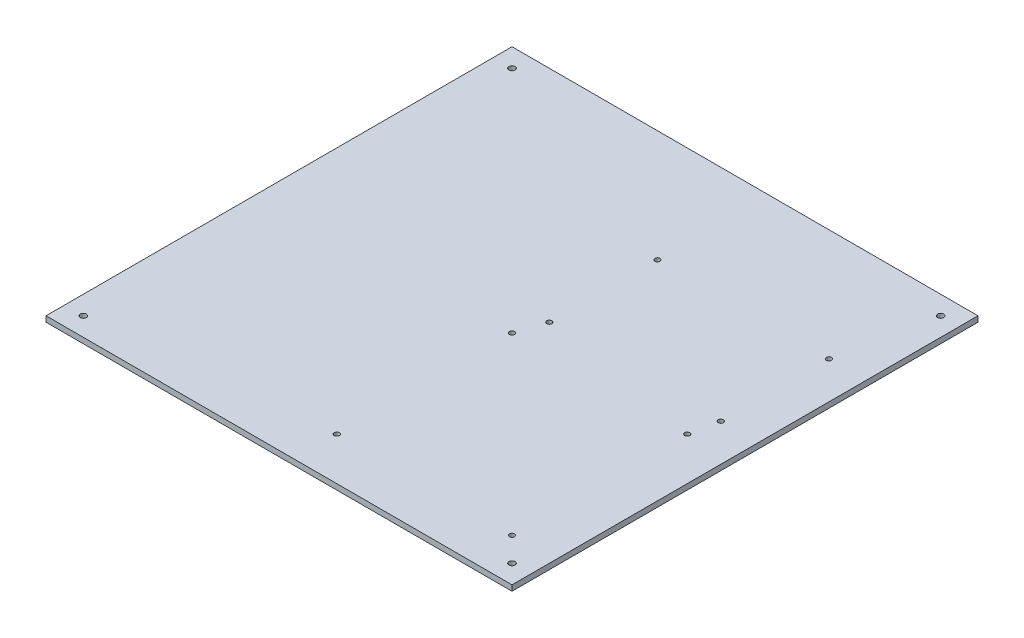
SolidWorks part; units mm, degrees
ref_plane "Front Plane" through (0, 0, 0) normal (0, 0, 1) x (1, 0, 0)
ref_plane "Top Plane" through (0, 0, 0) normal (0, 1, 0) x (1, 0, 0)
ref_plane "Right Plane" through (0, 0, 0) normal (1, 0, 0) x (0, 0, -1)
sketch "Sketch1" plane through (0, 0, 0) normal (0, 1, 0) x (1, 0, 0)
  line L0 (0, 0) -> (0, -250) construction
  line L1 (-125, 0) -> (125, 0)
  line L2 (-125, 0) -> (-125, -250)
  line L3 (-125, -250) -> (125, -250)
  line L4 (125, 0) -> (125, -250)
  line L5 (0, -1.65) -> (0, 1.65) construction
  line L6 (-125, -125) -> (125, -125) construction
  line L7 (55, -130) -> (55, -230) construction
  line L8 (-105, -161.34) -> (-31.34, -161.34) construction
  line L9 (-105, -15) -> (-31.34, -15) construction
  line L10 (-105, -15) -> (-105, -88.66) construction
  line L11 (-105, -88.66) -> (-31.34, -88.66) construction
  line L12 (-31.34, -15) -> (-31.34, -88.66) construction
  line L13 (-105, -161.34) -> (-105, -235) construction
  line L14 (-105, -235) -> (-31.34, -235) construction
  line L15 (-31.34, -161.34) -> (-31.34, -235) construction
  line L16 (-105, -88.66) -> (-105, -161.34) construction
  line L17 (5, -130) -> (105, -130) construction
  line L18 (5, -130) -> (5, -230) construction
  line L19 (5, -230) -> (105, -230) construction
  line L20 (105, -130) -> (105, -230) construction
  line L21 (5, -180) -> (105, -180) construction
  line L22 (-60.805, -122.8687) -> (-38.005, -122.8687) construction
  line L23 (9, -43) -> (109, -43) construction
  line L24 (9, -43) -> (9, -122) construction
  line L25 (9, -122) -> (109, -122) construction
  line L26 (109, -43) -> (109, -122) construction
  line L27 (-102.037, -122.1462) -> (-79.237, -122.1462) construction
  line L28 (-102.037, -122.1462) -> (-102.037, -145.0462) construction
  line L29 (-102.037, -145.0462) -> (-79.237, -145.0462) construction
  line L30 (-79.237, -122.1462) -> (-79.237, -145.0462) construction
  line L35 (-60.805, -122.8687) -> (-60.805, -145.7687) construction
  line L36 (-60.805, -145.7687) -> (-38.005, -145.7687) construction
  line L37 (-38.005, -122.8687) -> (-38.005, -145.7687) construction
  circle A3 centre (-115, -240) radius 1.65
  circle A4 centre (115, -240) radius 1.65
  circle A5 centre (-115, -10) radius 1.65
  circle A6 centre (115, -10) radius 1.65
  circle A7 centre (13, -60) radius 1.375
  circle A8 centre (13, -118) radius 1.375
  circle A9 centre (105, -118) radius 1.375
  circle A10 centre (105, -60) radius 1.375
  circle A11 centre (8, -133) radius 1.375
  circle A12 centre (102, -133) radius 1.375
  circle A13 centre (102, -227) radius 1.375
  circle A14 centre (8, -227) radius 1.375
  dimension "D1" = 3.3
  dimension "D2" = 10
  dimension "D12" = 2.75
  dimension "D20" = 2.75
  dimension "D3" = 10
  dimension "D4" = 250
  dimension "D5" = 250
  dimension "D6" = 73.66
  dimension "D7" = 15
  dimension "D8" = 20
  dimension "D9" = 58
  dimension "D10" = 92
  dimension "D11" = 58
  dimension "D13" = 20
  dimension "D14" = 60
  dimension "D15" = 100
  dimension "D16" = 100
  dimension "D17" = 20
  dimension "D18" = 20
  dimension "D19" = 3
  dimension "D21" = 3
  dimension "D22" = 17
  dimension "D23" = 79
  dimension "D24" = 100
  dimension "D25" = 4
  dimension "D26" = 22.9
  dimension "D27" = 22.8
extrude "Boss-Extrude1" add sketch "Sketch1" along normal blind 3
equation "\"cf_tube_outer_diameter\"= 25mm"
equation "\"cf_tube_inner_diameter\" = 21mm"
equation "\"mid_plate_mid_to_top\" = 100mm"
equation "\"mid_plate_mid_to_bottom\" = 30mm"
equation "\"mid_plate_horizontal_spacing\"=250mm"
equation "\"cf_plate_thickness\" =3mm"
equation "\"mid_tube_length\" = 500mm"
equation "\"mid_plate_bottom_width\" = 180mm"
equation "\"mid_support_plate_distance\" = 250mm"
equation "\"nut_strip_2_hole_distance\" = 7mm"
equation "\"nut_strip_hole_diameter\" = 2.5mm"
equation "\"nut_strip_hole_to_edge_distance\"= 2.5mm"
